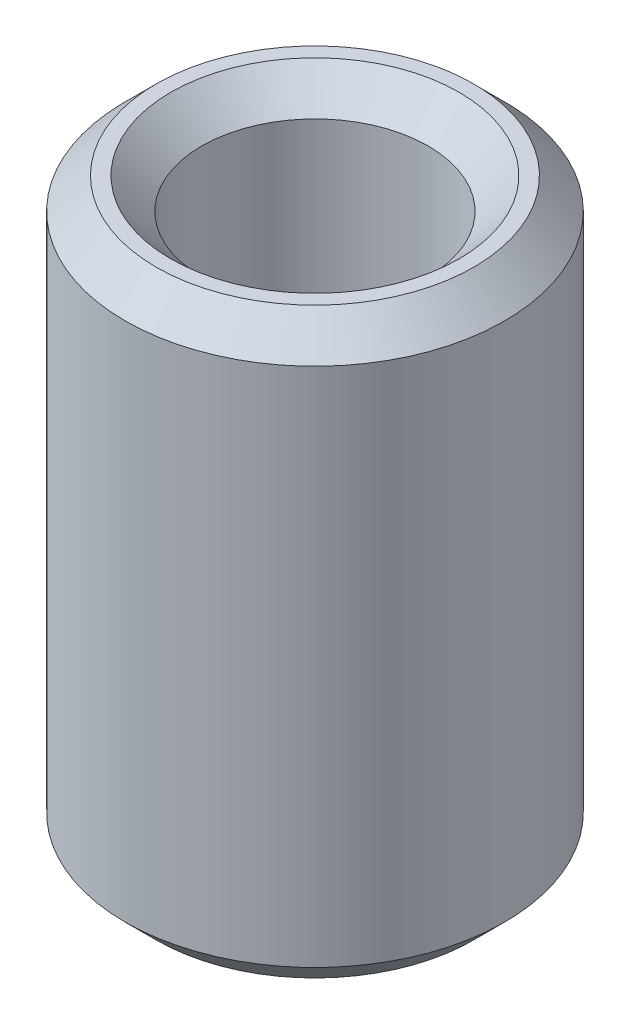
SolidWorks part; units mm, degrees
ref_plane "Front Plane" through (0, 0, 0) normal (0, 0, 1) x (1, 0, 0)
ref_plane "Top Plane" through (0, 0, 0) normal (0, 1, 0) x (1, 0, 0)
ref_plane "Right Plane" through (0, 0, 0) normal (1, 0, 0) x (0, 0, -1)
sketch "Sketch1" plane through (0, 0, 0) normal (0, 1, 0) x (1, 0, 0)
  circle A0 centre (0, 0) radius 22.5
  dimension "SLEEVE_OD" = 45
extrude "Boss-Extrude1" add sketch "Sketch1" along normal blind 69.0912
sketch "Sketch2" plane through (0, 0, 0) normal (0, 1, 0) x (1, 0, 0)
  circle A0 centre (0, 0) radius 13.4277
  dimension "BORE_D" = 26.8553
extrude "Cut-Extrude1" cut sketch "Sketch2" along normal through all
chamfer "Chamfer1" distance 3.6748 angle 45 4 edges at (0, 69.0912, 13.4277) (0, 0, 13.4277) (0, 0, 22.5) (0, 69.0912, 22.5)
